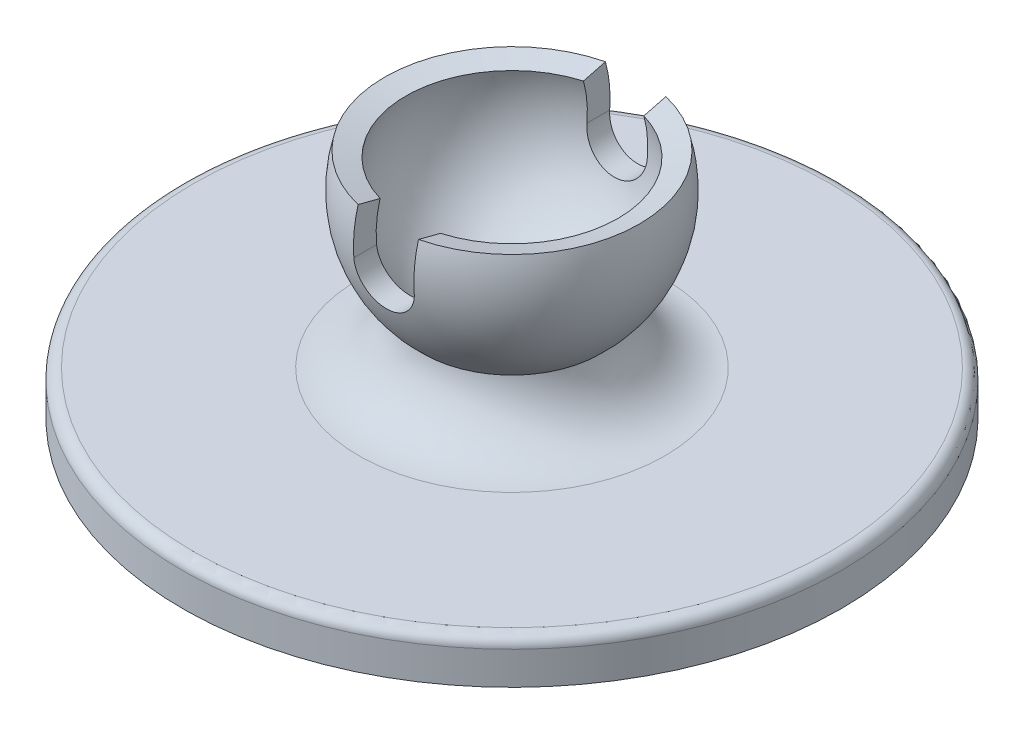
SolidWorks part; units mm, degrees
ref_plane "Face" through (0, 0, 0) normal (0, 0, 1) x (1, 0, 0)
ref_plane "Dessus" through (0, 0, 0) normal (0, 1, 0) x (1, 0, 0)
ref_plane "Droite" through (0, 0, 0) normal (1, 0, 0) x (0, 0, -1)
sketch "Sketch2" plane through (0, 0, 0) normal (0, 0, 1) x (1, 0, 0)
  line L0 (0, 0) -> (4, 0)
  line L1 (4, 0) -> (4, 2.5279)
  line L4 (0, 2) -> (0, 0)
  line L5 (5.7956, 8.5529) -> (4.8296, 8.2941)
  line L6 (4.8296, 8.2941) -> (0, 7) construction
  line L7 (0, 7) -> (0, 2) construction
  arc A0 (4.8296, 8.2941) -> (0, 2) centre (0, 7) cw
  arc A1 (5.7956, 8.5529) -> (4, 2.5279) centre (0, 7) cw
  dimension "D1" = 5
  dimension "D4" = 105
  dimension "D2" = 1
  dimension "D3" = 4
  dimension "D5" = 2
  dimension "D6" = 4.8296
revolve "Revolve2" add sketch "Sketch2" angle 360 about L4
sketch "Sketch3" plane through (0, 0, 0) normal (0, -1, 0) x (1, 0, 0)
  circle A0 centre (0, 0) radius 15
  dimension "D1" = 30
extrude "Boss-Extrude1" add sketch "Sketch3" along normal blind 2
sketch "Sketch6" plane through (0, 0, 0) normal (0, 0, 1) x (1, 0, 0)
  line L0 (0, 0) -> (0, 8.5529) construction
  line L1 (-5.7956, 8.5529) -> (5.7956, 8.5529) construction
  line L2 (1.375, 6.5529) -> (1.375, 8.5529)
  line L3 (1.375, 8.5529) -> (-1.375, 8.5529)
  line L4 (-1.375, 8.5529) -> (-1.375, 6.5529)
  arc A0 (-1.375, 6.5529) -> (1.375, 6.5529) centre (0, 6.5529) ccw
  dimension "D1" = 2.75
  dimension "D2" = 2
extrude "Cut-Extrude1" cut sketch "Sketch6" against normal through all both and the other way through all
fillet "Fillet1" radius 3 1 edges at (-4, 0, 0)
fillet "Fillet2" radius 0.5 1 edges at (15, 0, 0)
